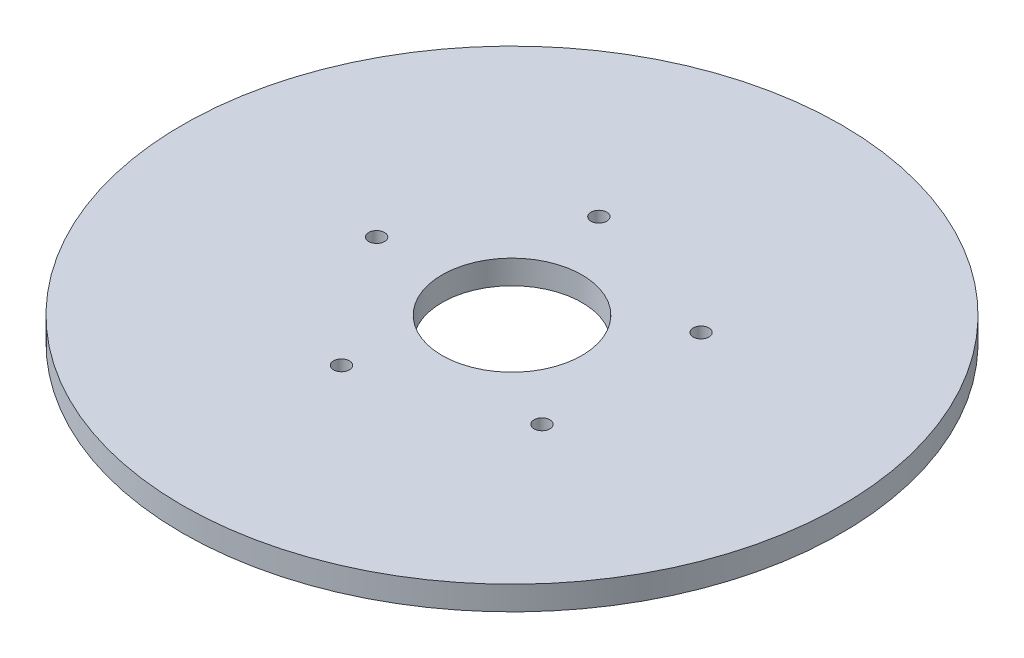
SolidWorks part; units mm, degrees
ref_plane "Front Plane" through (0, 0, 0) normal (0, 0, 1) x (1, 0, 0)
ref_plane "Top Plane" through (0, 0, 0) normal (0, 1, 0) x (1, 0, 0)
ref_plane "Right Plane" through (0, 0, 0) normal (1, 0, 0) x (0, 0, -1)
sketch "Sketch1" plane through (0, 0, 0) normal (0, 1, 0) x (1, 0, 0)
  circle A0 centre (0, 0) radius 82.5
  dimension "FLANGE_OD" = 165
extrude "Boss-Extrude1" add sketch "Sketch1" along normal blind 6
sketch "Sketch2" plane through (0, 0, 0) normal (0, 1, 0) x (1, 0, 0)
  circle A0 centre (0, 0) radius 17.5
  dimension "BORE_D" = 35
extrude "Cut-Extrude1" cut sketch "Sketch2" along normal through all
sketch "Sketch3" plane through (0, 6, 0) normal (0, 1, 0) x (1, 0, 0)
  circle A0 centre (0, 0) radius 33.8844 construction
  circle A1 centre (-33.8844, 0) radius 1.9803
  dimension "BOLT_D" = 3.9605
  dimension "BOLT_PCD" = 67.7689
extrude "Cut-Extrude2" cut sketch "Sketch3" against normal blind 3.8122
pattern_circular "CirPattern1" count 5 over 360 about axis through (0, 0, 0) along (0, 1, 0) of "Cut-Extrude2"
